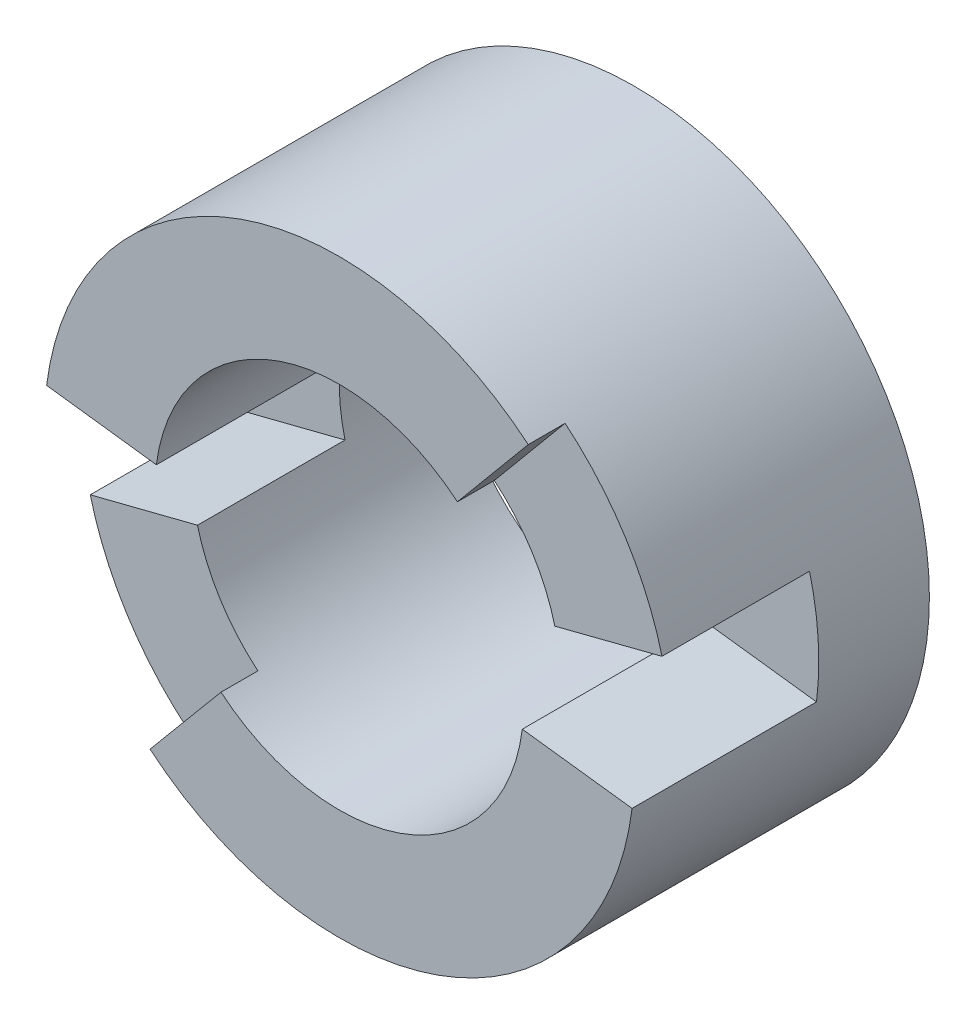
SolidWorks part; units mm, degrees
ref_plane "Front Plane" through (0, 0, 0) normal (0, 0, 1) x (1, 0, 0)
ref_plane "Top Plane" through (0, 0, 0) normal (0, 1, 0) x (1, 0, 0)
ref_plane "Right Plane" through (0, 0, 0) normal (1, 0, 0) x (0, 0, -1)
sketch "Sketch1" plane through (0, 0, 0) normal (0, 0, 1) x (1, 0, 0)
  circle A0 centre (0, 0) radius 5
  circle A1 centre (0, 0) radius 8
  dimension "D1" = 10
  dimension "D2" = 16
extrude "Boss-Extrude1" add sketch "Sketch1" along normal blind 8
sketch "Sketch2" plane through (0, 0, 0) normal (0, 1, 0) x (1, 0, 0)
  line L0 (10.56, -3) -> (13.56, -3)
  line L1 (10.56, -7) -> (10.56, -3)
  line L2 (-11.56, -8) -> (-11.56, -3)
  line L3 (-11.56, -3) -> (-14.56, -3)
  line L4 (-14.56, -3) -> (-14.56, -7)
  line L6 (13.56, -3) -> (13.56, -8)
  line L8 (5.56, -8) -> (13.56, -8)
  line L9 (5.56, -8) -> (5.56, -7)
  line L10 (5.56, -7) -> (10.56, -7)
  line L13 (-19.56, -8) -> (-11.56, -8)
  line L14 (-19.56, -8) -> (-19.56, -7)
  line L15 (-19.56, -7) -> (-14.56, -7)
  dimension "D2" = 8
  dimension "D3" = 11.56
  dimension "D4" = 3
  dimension "D5" = 3
  dimension "D6" = 3
  dimension "D7" = 1
  dimension "D9" = 5.56
  dimension "D10" = 8
  dimension "D11" = 1
  dimension "D12" = 5
wrap "Wrap2" sketch "Sketch2" wrap type deboss source sketch "Sketch2" thickness 4 face at (8, 0, 8) parameters "D1"=4
